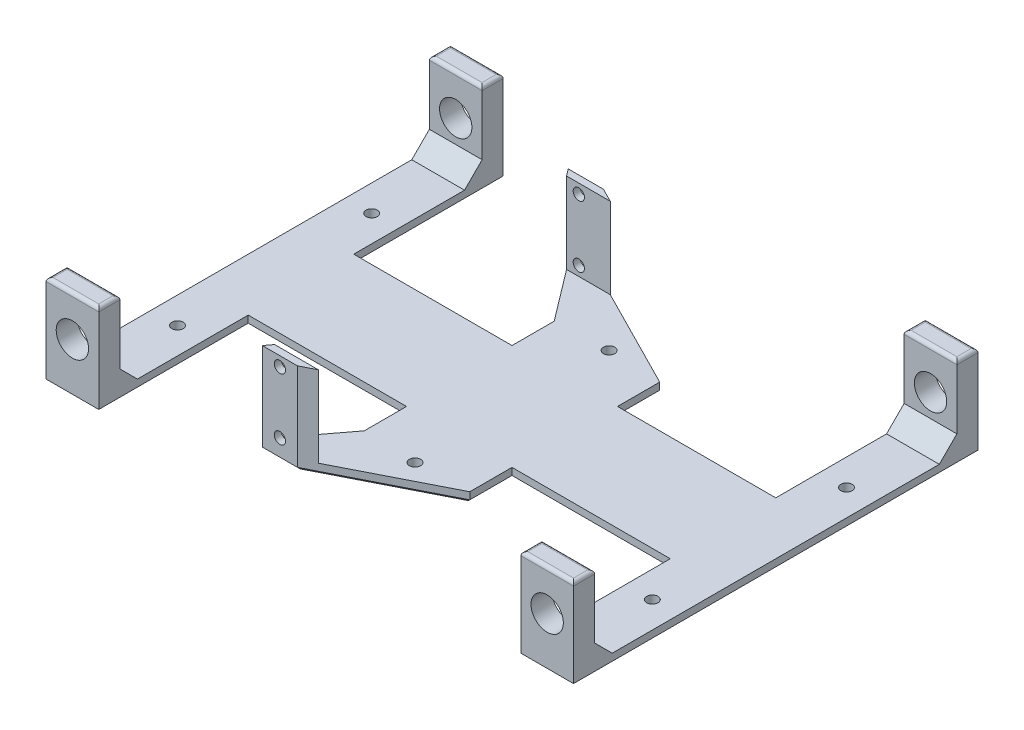
SolidWorks part; units mm, degrees
ref_plane "Front Plane" through (0, 0, 0) normal (0, 0, 1) x (1, 0, 0)
ref_plane "Top Plane" through (0, 0, 0) normal (0, 1, 0) x (1, 0, 0)
ref_plane "Right Plane" through (0, 0, 0) normal (1, 0, 0) x (0, 0, -1)
sketch "Sketch1" plane through (0, 0, 0) normal (0, 1, 0) x (1, 0, 0)
  line L0 (-67.5, 0) -> (67.5, 0) construction
  line L1 (-70, 25) -> (70, 25) construction
  line L2 (-70, 25) -> (-70, -25) construction
  line L3 (-70, -25) -> (70, -25) construction
  line L4 (70, 25) -> (70, -25) construction
  line L5 (-70, 25) -> (70, -25) construction
  line L6 (-70, -25) -> (70, 25) construction
  line L7 (-15, 27) -> (15, 27)
  line L8 (-15, 27) -> (-15, -27)
  line L9 (-15, -27) -> (15, -27)
  line L10 (15, 27) -> (15, -27)
  line L11 (-15, 27) -> (15, -27) construction
  line L12 (-15, -27) -> (15, 27) construction
  line L13 (-75, 57.5) -> (-75, -57.5)
  line L14 (-75, 27) -> (-60, 27)
  line L15 (-75, 27) -> (-75, -27)
  line L16 (-75, -27) -> (-60, -27)
  line L17 (-60, 27) -> (-60, -27)
  line L18 (-75, 27) -> (-60, -27) construction
  line L19 (-75, -27) -> (-60, 27) construction
  line L20 (-75, 51.5) -> (-60, 51.5)
  line L21 (-27.5, 43.5) -> (-17.5, 43.5)
  line L22 (-22.5, 73.5) -> (-22.5, 48.1057) construction
  line L23 (-27.5, 43.5) -> (-15, 27)
  line L24 (-17.5, 43.5) -> (15, 27)
  line L26 (-75, 57.5) -> (-60, 57.5)
  line L27 (-60, 57.5) -> (-60, 27)
  point P0 (0, 0)
  point P5 (0, 0)
  point P23 (-75, 0)
  point P27 (-22.5, 43.5)
  dimension "D1" = 50
  dimension "D2" = 140
  dimension "D3" = 54
  dimension "D4" = 135
  dimension "D5" = 5
  dimension "D6" = 30
  dimension "D7" = 6
  dimension "D8" = 115
  dimension "D9" = 14
  dimension "D10" = 45
  dimension "D11" = 10
sketch "Sketch2" plane through (0, 0, 0) normal (0, 1, 0) x (1, 0, 0)
  line L0 (-75, 57.5) -> (-60, 57.5) construction
  line L1 (-75, 57.5) -> (-75, -57.5) construction
  line L2 (-75, 51.5) -> (-60, 51.5) construction
  line L3 (-60, 57.5) -> (-60, 27) construction
  line L4 (-75, 27) -> (-60, 27) construction
  line L5 (-60, 27) -> (-60, -27) construction
  line L6 (-75, -27) -> (-60, -27) construction
  line L7 (-15, 27) -> (-15, -27) construction
  line L8 (-15, -27) -> (15, -27) construction
  line L9 (15, 27) -> (15, -27) construction
  line L10 (-15, 27) -> (15, 27) construction
  line L11 (-27.5, 43.5) -> (-15, 27) construction
  line L12 (-27.5, 43.5) -> (-17.5, 43.5) construction
  line L13 (-17.5, 43.5) -> (15, 27) construction
  line L14 (-75, 57.5) -> (-60, 57.5)
  line L15 (-75, 57.5) -> (-75, -57.5)
  line L16 (-75, 51.5) -> (-60, 51.5) construction
  line L17 (-60, 57.5) -> (-60, 27)
  line L18 (-75, 27) -> (-60, 27) construction
  line L19 (-60, 27) -> (-60, -27)
  line L20 (-75, -27) -> (-60, -27)
  line L21 (-15, 27) -> (-15, -27)
  line L22 (-15, -27) -> (15, -27)
  line L23 (15, 27) -> (15, -27)
  line L24 (-15, 27) -> (15, 27) construction
  line L25 (-27.5, 43.5) -> (-15, 27)
  line L26 (-27.5, 43.5) -> (-17.5, 43.5)
  line L27 (-17.5, 43.5) -> (15, 27)
  line L28 (0, 25) -> (0, -25) construction
  line L29 (-70, 25) -> (70, 25) construction
  line L30 (-70, -25) -> (70, -25) construction
  line L31 (-67.5, 0) -> (67.5, 0) construction
  line L32 (-67.5, 0) -> (67.5, 0) construction
  line L33 (75, -27) -> (60, -27)
  line L34 (75, 57.5) -> (60, 57.5)
  line L35 (60, 57.5) -> (60, 27)
  line L36 (75, 57.5) -> (75, -57.5)
  line L37 (60, 27) -> (60, -27)
  line L38 (75, -57.5) -> (60, -57.5)
  line L39 (60, -57.5) -> (60, -27)
  line L40 (-75, -57.5) -> (-60, -57.5)
  line L41 (-60, -57.5) -> (-60, -27)
  line L42 (-17.5, -43.5) -> (15, -27)
  line L43 (-27.5, -43.5) -> (-15, -27)
  line L44 (-27.5, -43.5) -> (-17.5, -43.5)
  line L46 (-67.5, 15) -> (67.5, 15)
  line L47 (-67.5, 15) -> (-67.5, -15)
  line L48 (-67.5, -15) -> (67.5, -15)
  line L49 (67.5, 15) -> (67.5, -15)
  line L50 (-67.5, 15) -> (67.5, -15) construction
  line L51 (-67.5, -15) -> (67.5, 15) construction
  point P33 (0, 0)
  dimension "D1" = 30
extrude "Boss-Extrude1" add sketch "Sketch2" along normal blind 3 contours L40 L41 L20 L15 | L48 L47 L46 L19 L17 L14 L15 L20 | L47 L48 L19 L46 | L19 L48 L21 L46 | L21 L48 L23 L46 | L21 L46 L23 L27 L26 L25 | L43 L44 L42 L22 | L48 L21 L22 L23 | L23 L48 L37 L46 | L49 L46 L37 L48 | L46 L49 L48 L37 L33 L36 L34 L35 | L39 L38 L36 L33 region at (-68.3094, 0, -18.5414) region at (-67.5, 0, 42.25) region at (-37.5, 0, 0) region at (-63.75, 0, 0) region at (0, 0, 0) region at (-4.4837, 0, -27.1576) region at (0, 0, 21) region at (37.5, 0, 0) region at (-9.375, 0, 33.875) region at (63.75, 0, 0) region at (68.3094, 0, -18.5414) region at (67.5, 0, 42.25)
sketch "Sketch3" plane through (0, 3, 0) normal (0, 1, 0) x (1, 0, 0)
  line L0 (-75, 57.5) -> (-60, 57.5) construction
  line L1 (-75, 51.5) -> (-60, 51.5) construction
  line L2 (-75, 57.5) -> (-75, -57.5) construction
  line L3 (-60, 57.5) -> (-60, 27) construction
  line L4 (-27.5, 43.5) -> (-17.5, 43.5) construction
  line L5 (-27.5, 43.5) -> (-15, 27) construction
  line L6 (-17.5, 43.5) -> (15, 27) construction
  line L7 (-75, 57.5) -> (-60, 57.5)
  line L8 (-75, 51.5) -> (-60, 51.5)
  line L9 (-75, 57.5) -> (-75, -57.5)
  line L10 (-60, 57.5) -> (-60, 27)
  line L11 (-27.5, 43.5) -> (-17.5, 43.5)
  line L12 (-27.5, 43.5) -> (-15, 27)
  line L13 (-17.5, 43.5) -> (15, 27)
  line L14 (-25.9848, 41.5) -> (-13.5606, 41.5)
  line L15 (0, 0) -> (0, 64.6874) construction
  line L16 (60, 57.5) -> (60, 27)
  line L17 (75, 57.5) -> (75, -57.5)
  line L18 (75, 51.5) -> (60, 51.5)
  line L19 (75, 57.5) -> (60, 57.5)
  line M12 (75, 57.5) -> (60, 57.5)
  line M13 (60, 57.5) -> (60, 15)
  line M17 (-17.5, 43.5) -> (-27.5, 43.5)
  line M18 (-27.5, 43.5) -> (-15, 27)
  line M21 (-60, 15) -> (-60, 57.5)
  line M22 (-60, 57.5) -> (-75, 57.5)
  line M23 (-75, 57.5) -> (-75, -57.5)
  dimension "D1" = 2
extrude "Boss-Extrude2" add sketch "Sketch3" along normal blind 23 contours L8 M23 M21 M22 | L14 L13 M18 M17 | L18 L17 M12 M13 region at (-67.5, 3, -54.5) region at (-21.0872, 3, -42.464) region at (67.5, 3, -54.5)
sketch "Sketch4" plane through (0, 0, -43.5) normal (0, 0, -1) x (-1, 0, 0)
  line L0 (22.5, 3) -> (22.5, 26) construction
  line L1 (17.5, 26) -> (27.5, 26) construction
  line L2 (22.5, 14.5) -> (10.7403, 14.5) construction
  circle A0 centre (22.5, 23.25) radius 1.6
  circle A1 centre (22.5, 5.75) radius 1.6
  dimension "D1" = 3.2
  dimension "D2" = 3
  dimension "D3" = 8.75
extrude "Cut-Extrude1" cut sketch "Sketch4" against normal blind 23
sketch "Sketch5" plane through (0, 0, -57.5) normal (0, 0, -1) x (-1, 0, 0)
  line L0 (67.5, 3) -> (67.5, 26) construction
  line L2 (60, 26) -> (75, 26) construction
  line L3 (75, 0) -> (60, 0) construction
  circle A0 centre (67.5, 14.5) radius 4.6
  dimension "D2" = 9.2
  dimension "D1" = 3
extrude "Cut-Extrude2" cut sketch "Sketch5" against normal blind 23
mirror "Mirror3" about plane through (0, 0, 0) normal (1, 0, 0) of "Cut-Extrude2"
mirror "Mirror4" about plane through (0, 0, 0) normal (0, 0, 1) of bodies 105
sketch "Sketch6" plane through (0, 3, 0) normal (0, 1, 0) x (1, 0, 0)
  line L0 (-70, 25) -> (70, 25) construction
  line L1 (0, 0) -> (0, 20.5507) construction
  line L2 (-67.5, 0) -> (67.5, 0) construction
  line L3 (-67.5, 0) -> (67.5, 0)
  circle A0 centre (-67.5, 27.6) radius 1.6
  circle A1 centre (0, 27.6) radius 1.6
  circle A2 centre (67.5, 27.6) radius 1.6
  circle A3 centre (67.5, -27.6) radius 1.6
  circle A4 centre (0, -27.6) radius 1.6
  circle A5 centre (-67.5, -27.6) radius 1.6
  dimension "D1" = 3.2
  dimension "D2" = 3.2
  dimension "D3" = 2.6
extrude "Cut-Extrude3" cut sketch "Sketch6" against normal blind 23 contours A0 | A1 | A2 | A3 | A5 | A4
chamfer "Chamfer1" distance 1 angle 45 24 edges at (-67.5, 0, 57.5) (-37.5, 0, 15) (-15, 0, 21) (-21.25, 0, 35.25) (-22.5, 0, 43.5) (-1.25, 0, 35.25) (15, 0, 21) (37.5, 0, 15) (60, 0, 36.25) (67.5, 0, 57.5) (75, 0, 0) (67.5, 0, -57.5) (60, 0, -36.25) (37.5, 0, -15) (15, 0, -21) (-1.25, 0, -35.25) (-22.5, 0, -43.5) (-21.25, 0, -35.25) (-15, 0, -21) (-37.5, 0, -15) (-60, 0, -36.25) (-67.5, 0, -57.5) (-75, 0, 0) (-60, 0, 36.25)
fillet "Fillet1" radius 1 16 edges at (75, 26, 54.5) (67.5, 26, 57.5) (60, 26, 54.5) (67.5, 26, 51.5) (60, 26, -54.5) (67.5, 26, -57.5) (75, 26, -54.5) (67.5, 26, -51.5) (-67.5, 26, -57.5) (-60, 26, -54.5) (-67.5, 26, -51.5) (-75, 26, -54.5) (-75, 26, 54.5) (-67.5, 26, 51.5) (-60, 26, 54.5) (-67.5, 26, 57.5)
sketch "Sketch7" plane through (0, 0, 0) normal (0, 1, 0) x (1, 0, 0)
  line L1 (-78.3123, -40.4384) -> (-51.524, -40.4384)
  line L2 (-78.3123, -40.4384) -> (-78.3123, -63.0409)
  line L3 (-78.3123, -63.0409) -> (-51.524, -63.0409)
  line L4 (-51.524, -40.4384) -> (-51.524, -63.0409)
  line L5 (-97.9445, 75.2696) -> (91.2474, 75.2696)
  line L6 (-97.9445, 75.2696) -> (-97.9445, -75.4783)
  line L7 (-97.9445, -75.4783) -> (91.2474, -75.4783)
  line L8 (91.2474, 75.2696) -> (91.2474, -75.4783)
extrude "Cut-Extrude4" [suppressed] cut sketch "Sketch7" along normal through all
chamfer "Chamfer2" distance 5 angle 45 4 edges at (67.5, 3, 51.5) (67.5, 3, -51.5)
